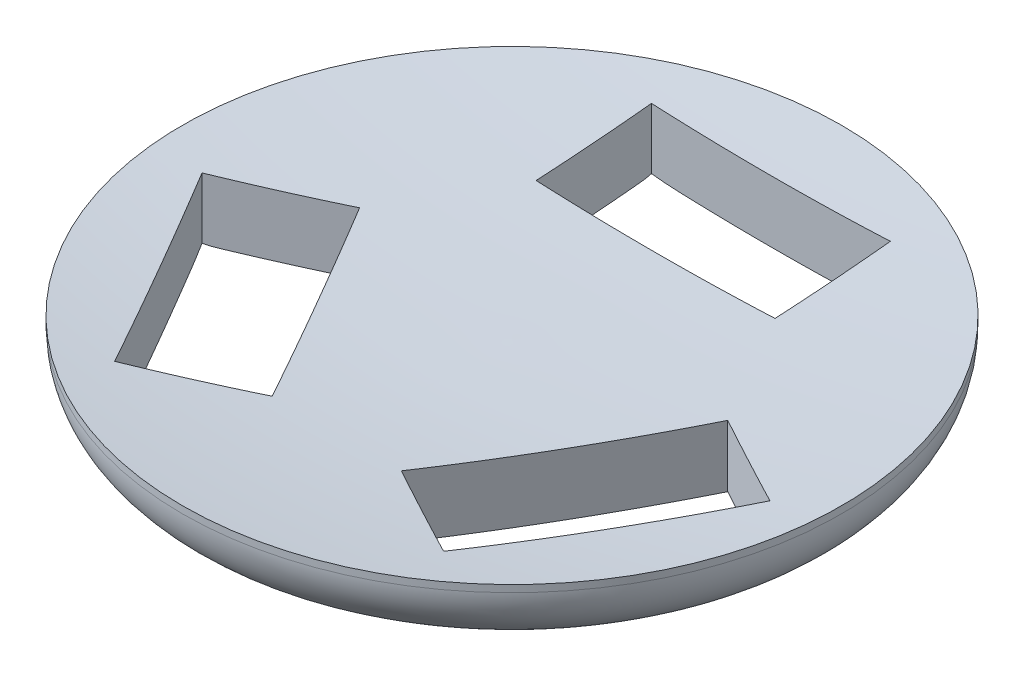
SolidWorks part; units mm, degrees
ref_plane "Front Plane" through (0, 0, 0) normal (0, 0, 1) x (1, 0, 0)
ref_plane "Top Plane" through (0, 0, 0) normal (0, 1, 0) x (1, 0, 0)
ref_plane "Right Plane" through (0, 0, 0) normal (1, 0, 0) x (0, 0, -1)
sketch "Sketch2" plane through (0, 0, 0) normal (0, 1, 0) x (1, 0, 0)
  line L0 (0, -68.0098) -> (0, 65.7503) construction
  line L1 (-29, 62.8517) -> (29, 62.8517)
  line L2 (-29, 62.8517) -> (-29, 34.8517)
  line L3 (-29, 34.8517) -> (29, 34.8517)
  line L4 (29, 62.8517) -> (29, 34.8517)
  line L5 (-29, 62.8517) -> (29, 34.8517) construction
  line L6 (-29, 34.8517) -> (29, 62.8517) construction
  line L7 (-70.2148, 0) -> (95.7201, 0) construction
  line L8 (0, 0) -> (-72.5813, -41.9048) construction
  line L9 (0, 0) -> (72.5813, -41.9048) construction
  line L10 (68.9311, -6.3111) -> (39.9311, -56.5406)
  line L11 (44.6824, 7.6889) -> (15.6824, -42.5406)
  line L12 (68.9311, -6.3111) -> (44.6824, 7.6889)
  line L13 (39.9311, -56.5406) -> (15.6824, -42.5406)
  line L14 (-39.9311, -56.5406) -> (-68.9311, -6.3111)
  line L15 (-15.6824, -42.5406) -> (-44.6824, 7.6889)
  line L16 (-39.9311, -56.5406) -> (-15.6824, -42.5406)
  line L17 (-68.9311, -6.3111) -> (-44.6824, 7.6889)
  line L18 (-6.5, 0.8517) -> (6.5, 34.8517) construction
  line L19 (-6.5, 34.8517) -> (6.5, 34.8517)
  line L20 (-6.5, 34.8517) -> (-6.5, 0.8517)
  line L21 (-6.5, 0.8517) -> (6.5, 0.8517)
  line L22 (6.5, 34.8517) -> (6.5, 0.8517)
  line L23 (-6.5, 34.8517) -> (6.5, 0.8517) construction
  line L24 (33.4324, -11.7967) -> (6.5, 3.7528)
  line L25 (1.4751, 0.8517) -> (0, -1.7033)
  line L26 (26.9324, -23.055) -> (0, -7.5056)
  line L27 (-26.9324, -23.055) -> (0, -7.5056)
  line L28 (0, -1.7033) -> (-1.4751, 0.8517)
  line L29 (-33.4324, -11.7967) -> (-6.5, 3.7528)
  circle A2 centre (0, 0) radius 16 construction
  point P3 (0, 17.8517)
  point P4 (0, 34.8517)
  point P6 (0, 48.8517)
  point P13 (0, 0)
  point P33 (0, 0)
  point P38 (0, 0)
  point P41 (0, 0)
  dimension "D1" = 34
  dimension "D2" = 13
  dimension "D3" = 32
  dimension "D5" = 58
  dimension "D6" = 120
  dimension "D7" = 28
  dimension "D8" = 3
  dimension "D4" = 3
sketch "Sketch3" plane through (0, 0, 0) normal (1, 0, 0) x (0, 0, -1)
  line L0 (0, 83.7838) -> (0, -101.0811) construction
  line L1 (-115.9459, 0) -> (127.2973, 0) construction
  line L3 (80, 18.2932) -> (80, 20)
  line L5 (0, 15) -> (0, 0)
  arc A0 (0, 0) -> (66.6276, 3.3818) centre (4.1976, 575.3378) ccw
  arc A1 (0, 15) -> (80, 20) centre (4.1976, 590.3378) ccw
  arc A2 (80, 18.2932) -> (66.6276, 3.3818) centre (65, 18.2932) cw
  point P13 (80, 5)
  dimension "D5" = 15
  dimension "D1" = 15
  dimension "D3" = 20
  dimension "D4" = 80
revolve "Revolve1" add sketch "Sketch3" angle 360 about L5
extrude "Cut-Extrude1" cut sketch "Sketch2" along normal blind 40 contours L3 L4 L1 L2 | L15 L17 L14 L16 | L11 L13 L10 L12
